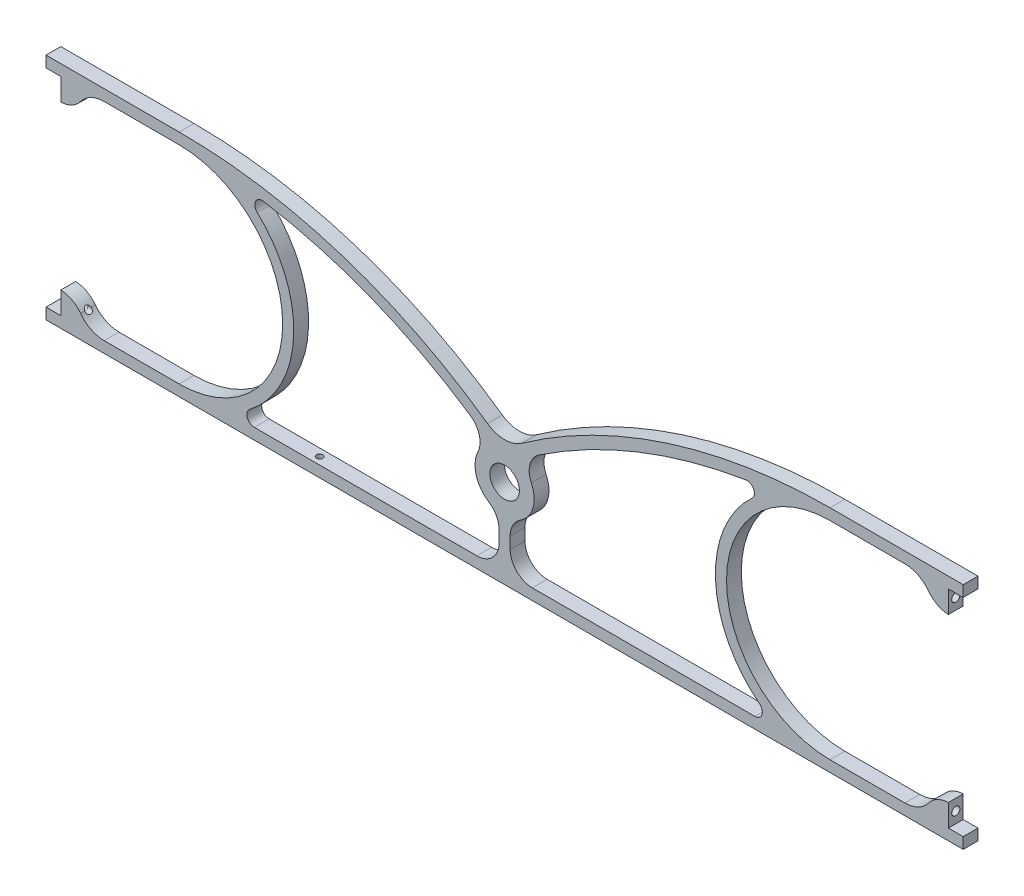
SolidWorks part; units mm, degrees
material "6061-T6 (SS)"
ref_plane "Front Plane" through (0, 0, 0) normal (0, 0, 1) x (1, 0, 0)
ref_plane "Top Plane" through (0, 0, 0) normal (0, 1, 0) x (1, 0, 0)
ref_plane "Right Plane" through (0, 0, 0) normal (1, 0, 0) x (0, 0, -1)
sketch "Sketch1" plane through (0, 0, 0) normal (0, 0, 1) x (1, 0, 0)
  line L0 (190.5, -38.1) -> (-190.5, -38.1)
  line L1 (-190.5, -38.1) -> (-190.5, -33.3375)
  line L2 (-190.5, -33.3375) -> (-118.5797, -33.3375)
  line L3 (0, 0) -> (0, 58.9425) construction
  line L4 (0, 0) -> (-90.0269, 0) construction
  line L5 (-190.5, 60.325) -> (-190.5, 55.5625)
  line L6 (-190.5, 60.325) -> (-139.7, 60.325)
  line L7 (-190.5, 55.5625) -> (-139.7, 55.5625)
  line L8 (-190.5, 11.1125) -> (-109.7015, 11.1125) construction
  line L9 (190.5, 60.325) -> (190.5, 55.5625)
  line L10 (190.5, -38.1) -> (190.5, -33.3375)
  line L11 (190.5, -33.3375) -> (-118.5797, -33.3375)
  line L12 (190.5, 60.325) -> (139.7, 60.325)
  line L13 (190.5, 55.5625) -> (139.7, 55.5625)
  line L14 (-190.5, 55.5625) -> (-196.85, 55.5625)
  line L15 (-196.85, 55.5625) -> (-196.85, 60.325)
  line L16 (-196.85, 60.325) -> (-190.5, 60.325)
  line L17 (-190.5, -33.3375) -> (-196.85, -33.3375)
  line L18 (-196.85, -33.3375) -> (-196.85, -38.1)
  line L19 (-196.85, -38.1) -> (-190.5, -38.1)
  line L20 (196.85, -38.1) -> (190.5, -38.1)
  line L21 (190.5, -33.3375) -> (196.85, -33.3375)
  line L22 (196.85, -33.3375) -> (196.85, -38.1)
  line L23 (196.85, 60.325) -> (190.5, 60.325)
  line L24 (196.85, 55.5625) -> (196.85, 60.325)
  line L25 (190.5, 55.5625) -> (196.85, 55.5625)
  line L26 (0, -12.7) -> (0, -33.3375) construction
  line L27 (-2.3813, -12.4748) -> (-2.3813, -33.3375)
  line L28 (2.3813, -12.4748) -> (2.3813, -33.3375)
  line L29 (-2.3813, -12.7) -> (-2.3813, -33.3375) construction
  line L30 (2.3813, -12.7) -> (2.3813, -33.3375) construction
  circle A0 centre (0, 0) radius 6.35
  circle A1 centre (0, 0) radius 12.7
  arc A2 (-139.7, -33.3375) -> (-139.7, 55.5625) centre (-139.7, 11.1125) ccw
  arc A3 (-118.5797, -33.3375) -> (-116.1418, 54.3199) centre (-139.7, 11.1125) ccw
  circle A4 centre (-139.7, 11.1125) radius 49.2125 construction
  circle A5 centre (-139.7, 11.1125) radius 44.45 construction
  arc A6 (0, 12.7) -> (-139.7, 60.325) centre (-139.7, -168.3808) ccw
  arc A7 (-5.9388, 11.2259) -> (-139.7, 55.5625) centre (-139.7, -168.3808) ccw
  arc A8 (118.5797, -33.3375) -> (116.1418, 54.3199) centre (139.7, 11.1125) cw
  arc A9 (139.7, -33.3375) -> (139.7, 55.5625) centre (139.7, 11.1125) cw
  arc A10 (5.9388, 11.2259) -> (139.7, 55.5625) centre (139.7, -168.3808) cw
  arc A11 (0, 12.7) -> (139.7, 60.325) centre (139.7, -168.3808) cw
  dimension "D1" = 4.7625
  dimension "D2" = 12.7
  dimension "D3" = 6.35
  dimension "D5" = 4.7625
  dimension "D7" = 50.8
  dimension "D4" = 381
  dimension "D6" = 88.9
  dimension "D8" = 6.35
  dimension "D9" = 38.1
  dimension "D10" = 2.3813
  dimension "D11" = 2.3813
extrude "Boss-Extrude1" add sketch "Sketch1" against normal blind 6.35 contours L18 L19 L1 L17 | L16 L15 L14 L5 | A7 A1 A6 L6 L5 L7 | A3 A7 A2 L2 | L10 L11 L2 L1 L0 | A1 A0 | A1 L27 L11 L28 | A11 A1 A10 L13 L9 L12 | A10 A8 L11 A9 | L9 L25 L24 L23 | L22 L21 L10 L20
sketch "Sketch2" plane through (0, 0, 0) normal (0, 0, 1) x (1, 0, 0)
  line L0 (-190.5, 55.5625) -> (-190.5, 46.0375)
  line L2 (-196.85, 55.5625) -> (-139.7, 55.5625) construction
  line L3 (-190.5, 46.0375) -> (-184.15, 46.0375)
  line L4 (-184.15, 46.0375) -> (-184.15, 55.5625)
  line L7 (-184.15, 55.5625) -> (-190.5, 55.5625)
  line L8 (-190.5, -33.3375) -> (-190.5, -23.8125)
  line L9 (-196.85, -33.3375) -> (-139.7, -33.3375) construction
  line L11 (-190.5, -23.8125) -> (-184.15, -23.8125)
  line L12 (-184.15, -23.8125) -> (-184.15, -33.3375)
  line L13 (-184.15, -33.3375) -> (-190.5, -33.3375)
  line L14 (-196.85, 55.5625) -> (-196.85, 60.325) construction
  line L15 (0, 0) -> (0, 66.1526) construction
  line L16 (184.15, -33.3375) -> (190.5, -33.3375)
  line L17 (184.15, -23.8125) -> (184.15, -33.3375)
  line L18 (190.5, -23.8125) -> (184.15, -23.8125)
  line L19 (190.5, -33.3375) -> (190.5, -23.8125)
  line L20 (184.15, 55.5625) -> (190.5, 55.5625)
  line L21 (184.15, 46.0375) -> (184.15, 55.5625)
  line L22 (190.5, 46.0375) -> (184.15, 46.0375)
  line L23 (190.5, 55.5625) -> (190.5, 46.0375)
  line L24 (-184.15, -33.3375) -> (-190.5, -33.3375)
  line M22 (196.85, -33.3375) -> (139.7, -33.3375)
  line M24 (139.7, 55.5625) -> (196.85, 55.5625)
  line M32 (-196.85, 55.5625) -> (-139.7, 55.5625)
  line M34 (-139.7, -33.3375) -> (-196.85, -33.3375)
  dimension "D1" = 6.35
  dimension "D2" = 6.35
  dimension "D3" = 9.525
extrude "Boss-Extrude2" add sketch "Sketch2" against normal up to surface (6.35 mm away) contours L12 L11 L8 M34 | L3 L4 L0 M32 | L23 L21 L22 M24 | L19 L18 L17 M22 up to face at (-44.814, -1.6402, -6.35)
fillet "Fillet1" radius 12.7 4 edges at (184.15, -33.3375, -3.175) (184.15, 55.5625, -3.175) (-184.15, -33.3375, -3.175) (-184.15, 55.5625, -3.175)
fillet "Fillet2" radius 11.1125 4 edges at (184.15, -23.8125, -3.175) (184.15, 46.0375, -3.175) (-184.15, -23.8125, -3.175) (-184.15, 46.0375, -3.175)
hole_wizard "#6-32 Tapped Hole1" positions "Sketch4" profile "Sketch3" tap size "#6-32" standard "ANSI Inch"
sketch "Sketch4" plane through (0, -38.1, 0) normal (0, -1, 0) x (-1, 0, 0)
  line L2 (196.85, 3.175) -> (-196.85, 3.175) construction
  line L3 (196.85, 6.35) -> (196.85, 0) construction
  line L4 (-196.85, 6.35) -> (-196.85, 0) construction
  point P14 (82.55, 3.175)
  dimension "D1" = 114.3
sketch "Sketch3" plane through (-82.55, -38.1, -3.175) normal (1, 0, 0) x (0, 0, -1)
  line L0 (0, 0) -> (0, 10.2107)
  line L1 (0, 10.2107) -> (1.3525, 9.398)
  line L2 (1.3525, 9.398) -> (1.3525, 0)
  line L5 (1.3525, 0) -> (0, 0)
  line L10 (0, 10.2107) -> (-1.3526, 9.398) construction
  line L11 (0, -6.35) -> (0, 107.95) construction
  dimension "Tap Drill Dia." = 2.7051
  dimension "Tap Drill Depth" = 9.398
  dimension "Drill Angle" = 118
cosmetic thread "Hole Thread1" parameters "D1"=4.7625, "D2"=3.5052
sketch "Sketch5" plane through (0, 0, -6.35) normal (0, 0, -1) x (-1, 0, 0)
  line L0 (20.4301, -20.4301) -> (20.4301, 20.4301) construction
  line L1 (20.4301, 20.4301) -> (-20.4301, 20.4301) construction
  line L2 (-20.4301, 20.4301) -> (-20.4301, -20.4301) construction
  line L3 (-20.4301, -20.4301) -> (20.4301, -20.4301) construction
  line L4 (20.4301, 20.4301) -> (-20.4301, -20.4301) construction
  circle A0 centre (-29.8444, 21.035) radius 2.2479 construction
  circle A1 centre (-29.8444, -21.035) radius 2.2479 construction
  circle A2 centre (29.8444, -21.035) radius 2.2479 construction
  circle A3 centre (29.8444, 21.035) radius 2.2479 construction
  circle A4 centre (-29.8444, 21.035) radius 2.2479
  circle A5 centre (-29.8444, -21.035) radius 2.2479
  circle A6 centre (29.8444, -21.035) radius 2.2479
  circle A7 centre (29.8444, 21.035) radius 2.2479
  circle A8 centre (0, 0) radius 28.8925 construction
  point P15 (20.4301, 20.4301)
  point P16 (-20.4301, 20.4301)
  point P17 (20.4301, -20.4301)
  point P18 (-20.4301, -20.4301)
  dimension "D1" = 57.785
  dimension "D2" = 45
hole_wizard "#4 Clearance Hole1" [suppressed] positions "Sketch8" profile "Sketch7" hole size "#4" standard "ANSI Inch"
sketch "Sketch8" plane through (0, 0, -6.35) normal (0, 0, -1) x (-1, 0, 0)
  point P0 (20.4301, 20.4301)
  point P3 (20.4301, -20.4301)
  point P6 (-20.4301, -20.4301)
  point P9 (-20.4301, 20.4301)
sketch "Sketch7" plane through (-20.4301, 20.4301, -6.35) normal (1, 0, 0) x (0, 1, 0)
  line L0 (0, 0) -> (0, 6.35)
  line L1 (0, 6.35) -> (1.6319, 6.35)
  line L2 (1.6319, 6.35) -> (1.6319, 0)
  line L5 (1.6319, 0) -> (0, 0)
  line L11 (0, -6.35) -> (0, 107.95) construction
  dimension "Thru Hole Dia." = 3.2639
  dimension "Thru Hole Depth" = 6.35
hole_wizard "#8 Clearance Hole1" [suppressed] positions "Sketch10" profile "Sketch11" hole size "#8" standard "ANSI Inch"
sketch "Sketch10" plane through (0, 0, -6.35) normal (0, 0, -1) x (-1, 0, 0)
  line L0 (25.4, 25.4) -> (-25.4, 25.4) construction
  line L2 (-25.4, -25.4) -> (25.4, -25.4) construction
  line L3 (25.4, -25.4) -> (25.4, 25.4) construction
  line L5 (-25.4, 25.4) -> (-25.4, -25.4) construction
  line L8 (-25.4, 25.4) -> (25.4, -25.4) construction
  point P2 (-25.4, 25.4)
  point P4 (25.4, 25.4)
  point P6 (25.4, -25.4)
  point P8 (-25.4, -25.4)
  dimension "D1" = 50.8
sketch "Sketch11" plane through (25.4, 25.4, -6.35) normal (1, 0, 0) x (0, 1, 0)
  line L0 (0, 0) -> (0, 6.35)
  line L1 (0, 6.35) -> (2.2479, 6.35)
  line L2 (2.2479, 6.35) -> (2.2479, 0)
  line L5 (2.2479, 0) -> (0, 0)
  line L11 (0, -6.35) -> (0, 107.95) construction
  dimension "Thru Hole Dia." = 4.4958
  dimension "Thru Hole Depth" = 6.35
fillet "Fillet3" radius 9.525 6 edges at (5.9388, 11.2259, -3.175) (-5.9388, 11.2259, -3.175) (2.3813, -33.3375, -3.175) (-2.3813, -33.3375, -3.175) (2.3813, -12.4748, -3.175) (-2.3813, -12.4748, -3.175)
fillet "Fillet4" radius 12.7 1 edges at (0, 12.7, -3.175)
hole_wizard "#6-32 Tapped Hole2" positions "Sketch13" profile "Sketch12" tap size "#6-32" standard "ANSI Inch"
sketch "Sketch13" plane through (190.5, 0, 0) normal (1, 0, 0) x (0, 0, -1)
  line L2 (0, -33.3375) -> (0, -23.8125) construction
  line L3 (6.35, -23.8125) -> (6.35, -33.3375) construction
  line L4 (0, -28.575) -> (6.35, -28.575) construction
  line L8 (0, 50.8) -> (6.35, 50.8) construction
  line L9 (0, 55.5625) -> (0, 46.0375) construction
  line L10 (6.35, 46.0375) -> (6.35, 55.5625) construction
  point P2 (3.175, -28.575)
  point P35 (3.175, 50.8)
sketch "Sketch12" plane through (190.5, -28.575, -3.175) normal (0, 1, 0) x (0, 0, -1)
  line L0 (0, 0) -> (0, 10.2107)
  line L1 (0, 10.2107) -> (1.3525, 9.398)
  line L2 (1.3525, 9.398) -> (1.3525, 7.112)
  line L3 (1.3525, 7.112) -> (1.7526, 7.112)
  line L4 (1.7526, 7.112) -> (1.7526, 0)
  line L5 (1.7526, 0) -> (0, 0)
  line L10 (0, 10.2107) -> (-1.3526, 9.398) construction
  line L11 (0, -6.35) -> (0, 107.95) construction
  dimension "Tap Drill Dia." = 2.7051
  dimension "Tap Drill Depth" = 9.398
  dimension "Thread Major Dia." = 3.5052
  dimension "Thread Depth" = 7.112
  dimension "Drill Angle" = 118
mirror "Mirror1" about plane through (0, 0, 0) normal (1, 0, 0) of "#6-32 Tapped Hole2"
fillet "Fillet5" radius 3.175 4 edges at (118.5797, -33.3375, -3.175) (116.1418, 54.3199, -3.175) (-118.5797, -33.3375, -3.175) (-116.1418, 54.3199, -3.175)
